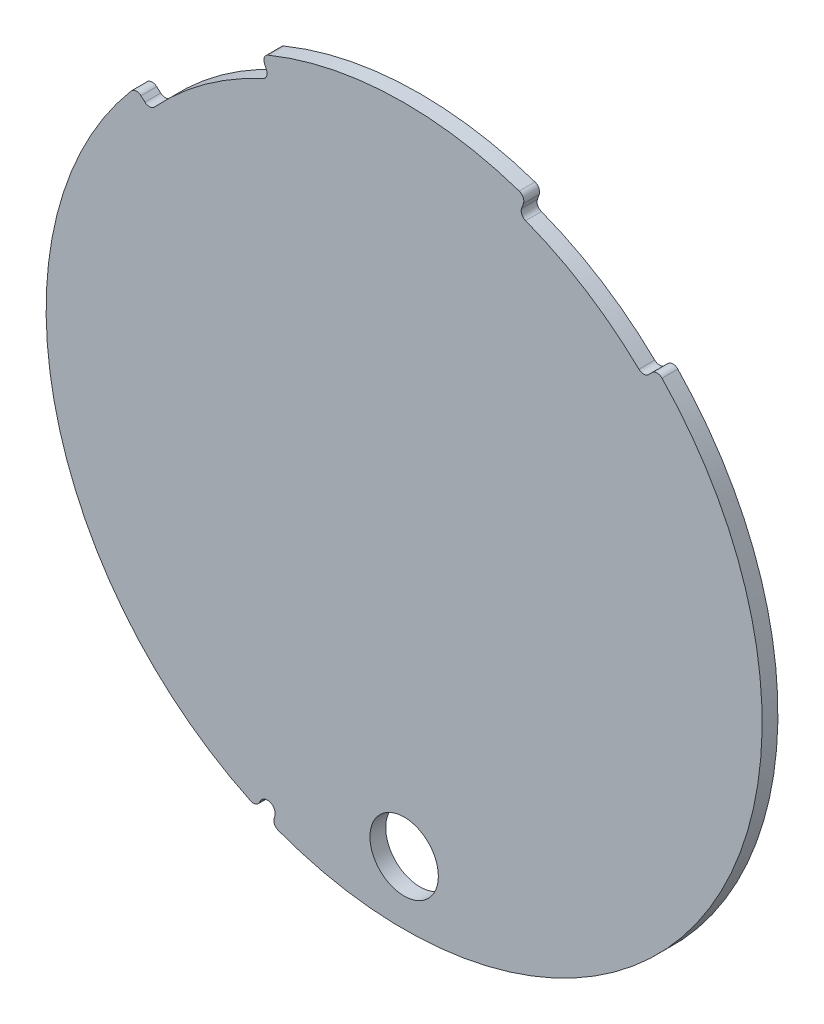
SolidWorks part; units mm, degrees
ref_plane "Alzado" through (0, 0, 0) normal (0, 0, 1) x (1, 0, 0)
ref_plane "Planta" through (0, 0, 0) normal (0, 1, 0) x (1, 0, 0)
ref_plane "Vista lateral" through (0, 0, 0) normal (1, 0, 0) x (0, 0, -1)
sketch "Model" plane through (0, 0, 0) normal (0, 0, 1) x (1, 0, 0)
  line L12 (23.9841, 23.7015) -> (20.8347, 18.3355)
  line L13 (20.8347, 18.3355) -> (9.1701, 24.9845)
  line L14 (9.1701, 24.9845) -> (11.9696, 30.4675)
  line L15 (11.9696, 30.4675) -> (23.9841, 23.7015)
  line L16 (23.5645, -22.1803) -> (11.6405, -29.0235)
  line L17 (11.6405, -29.0235) -> (8.6335, -23.7355)
  line L18 (8.6335, -23.7355) -> (20.4535, -16.8923)
  line L19 (20.4535, -16.8923) -> (23.5645, -22.1803)
  line L20 (-5.4405, -24.0979) -> (-8.4734, -29.4636)
  line L21 (-8.4734, -29.4636) -> (-20.5268, -22.4648)
  line L22 (-20.5268, -22.4648) -> (-17.5718, -17.1768)
  line L23 (-17.5718, -17.1768) -> (-5.4405, -24.0979)
  line L24 (6.9505, -26.589) -> (6.7665, -25.2108)
  line L25 (6.7665, -25.2108) -> (6.2386, -23.9493)
  line L26 (6.2386, -23.9493) -> (5.403, -22.8668)
  line L27 (5.403, -22.8668) -> (4.2959, -22.0254)
  line L28 (4.2959, -22.0254) -> (3.0068, -21.5041)
  line L29 (3.0068, -21.5041) -> (1.6493, -21.3393)
  line L30 (1.6493, -21.3393) -> (0.2952, -21.5305)
  line L31 (0.2952, -21.5305) -> (-0.9834, -22.077)
  line L32 (-0.9834, -22.077) -> (-2.0739, -22.9397)
  line L33 (-2.0739, -22.9397) -> (-2.8882, -24.0384)
  line L34 (-2.8882, -24.0384) -> (-3.3914, -25.31)
  line L35 (-3.3914, -25.31) -> (-3.5485, -26.6915)
  line L36 (-4.4685, -32.0246) -> (-3.5485, -26.6915)
  line L37 (7.8915, -32.0205) -> (11.0678, -31.275)
  line L38 (11.0678, -31.275) -> (14.108, -30.2492)
  line L39 (14.108, -30.2492) -> (16.9999, -28.9593)
  line L40 (16.9999, -28.9593) -> (19.7314, -27.4213)
  line L41 (19.7314, -27.4213) -> (22.2902, -25.6513)
  line L42 (22.2902, -25.6513) -> (24.6641, -23.6655)
  line L43 (24.6641, -23.6655) -> (26.841, -21.4799)
  line L44 (26.841, -21.4799) -> (28.8088, -19.1106)
  line L45 (28.8088, -19.1106) -> (30.5551, -16.5737)
  line L46 (30.5551, -16.5737) -> (32.0679, -13.8853)
  line L47 (32.0679, -13.8853) -> (33.3349, -11.0616)
  line L48 (33.3349, -11.0616) -> (34.344, -8.1185)
  line L49 (34.344, -8.1185) -> (35.083, -5.0721)
  line L50 (35.083, -5.0721) -> (35.5397, -1.9387)
  line L51 (35.5397, -1.9387) -> (35.702, 1.2658)
  line L52 (35.702, 1.2658) -> (35.5575, 4.5252)
  line L53 (35.5575, 4.5252) -> (35.105, 7.7563)
  line L54 (35.105, 7.7563) -> (34.3609, 10.8774)
  line L55 (34.3609, 10.8774) -> (33.3403, 13.875)
  line L56 (33.3403, 13.875) -> (32.058, 16.7354)
  line L57 (32.058, 16.7354) -> (30.5289, 19.445)
  line L58 (30.5289, 19.445) -> (28.7681, 21.9903)
  line L59 (28.7681, 21.9903) -> (26.7902, 24.3576)
  line L60 (26.7902, 24.3576) -> (24.6104, 26.5334)
  line L61 (24.6104, 26.5334) -> (22.2435, 28.504)
  line L62 (22.2435, 28.504) -> (19.7044, 30.2558)
  line L63 (19.7044, 30.2558) -> (17.008, 31.7752)
  line L64 (17.008, 31.7752) -> (14.1693, 33.0487)
  line L65 (14.1693, 33.0487) -> (11.2032, 34.0627)
  line L66 (11.2032, 34.0627) -> (8.1245, 34.8034)
  line L67 (8.1245, 34.8034) -> (4.9482, 35.2574)
  line L68 (4.9482, 35.2574) -> (1.6892, 35.411)
  line L69 (1.6892, 35.411) -> (-1.5698, 35.2552)
  line L70 (-1.5698, 35.2552) -> (-4.7458, 34.7991)
  line L71 (-4.7458, 34.7991) -> (-7.824, 34.0563)
  line L72 (-7.824, 34.0563) -> (-10.7894, 33.0405)
  line L73 (-10.7894, 33.0405) -> (-13.6273, 31.7651)
  line L74 (-13.6273, 31.7651) -> (-16.3227, 30.2438)
  line L75 (-16.3227, 30.2438) -> (-18.8606, 28.4903)
  line L76 (-18.8606, 28.4903) -> (-21.2262, 26.5182)
  line L77 (-21.2262, 26.5182) -> (-23.4046, 24.341)
  line L78 (-23.4046, 24.341) -> (-25.3808, 21.9723)
  line L79 (-25.3808, 21.9723) -> (-27.14, 19.4259)
  line L80 (-27.14, 19.4259) -> (-28.6673, 16.7153)
  line L81 (-28.6673, 16.7153) -> (-29.9477, 13.854)
  line L82 (-29.9477, 13.854) -> (-30.9663, 10.8558)
  line L83 (-30.9663, 10.8558) -> (-31.7083, 7.7341)
  line L84 (-31.7083, 7.7341) -> (-32.1587, 4.5028)
  line L85 (-32.1587, 4.5028) -> (-32.301, 1.2432)
  line L86 (-32.301, 1.2432) -> (-32.1366, -1.9611)
  line L87 (-32.1366, -1.9611) -> (-31.6779, -5.0943)
  line L88 (-31.6779, -5.0943) -> (-30.9369, -8.1401)
  line L89 (-30.9369, -8.1401) -> (-29.9258, -11.0825)
  line L90 (-29.9258, -11.0825) -> (-28.6569, -13.9055)
  line L91 (-28.6569, -13.9055) -> (-27.1423, -16.5929)
  line L92 (-27.1423, -16.5929) -> (-25.3943, -19.1286)
  line L93 (-25.3943, -19.1286) -> (-23.425, -21.4966)
  line L94 (-23.425, -21.4966) -> (-21.2466, -23.6807)
  line L95 (-21.2466, -23.6807) -> (-18.8713, -25.665)
  line L96 (-18.8713, -25.665) -> (-16.3114, -27.4332)
  line L97 (-16.3114, -27.4332) -> (-13.5789, -28.9694)
  line L98 (-13.5789, -28.9694) -> (-10.6861, -30.2574)
  line L99 (-10.6861, -30.2574) -> (-7.6453, -31.2812)
  line L100 (-7.6453, -31.2812) -> (-4.4685, -32.0246)
  line L101 (6.9505, -26.589) -> (7.8915, -32.0205)
  point P1 (-4.4685, -32.0246)
  point P2 (-10.7894, 33.0405)
sketch "Croquis3" plane through (0, 0, 0) normal (0, 0, 1) x (1, 0, 0)
  line L0 (-19.3008, -18.5746) -> (-7.1406, -25.5122) construction
  line L1 (-19.3008, -18.5746) -> (-22.3732, -23.9598) construction
  line L2 (-7.1406, -25.5122) -> (-10.213, -30.8974) construction
  line L3 (-22.3732, -23.9598) -> (-10.213, -30.8974) construction
  line L4 (6.9334, -25.1498) -> (19.0493, -18.1352) construction
  line L5 (6.9334, -25.1498) -> (10.0398, -30.5154) construction
  line L6 (19.0493, -18.1352) -> (22.1558, -23.5009) construction
  line L7 (10.0398, -30.5154) -> (22.1558, -23.5009) construction
  line L8 (10.2361, 28.9943) -> (22.4348, 22.1246) construction
  line L9 (10.2361, 28.9943) -> (7.1938, 23.592) construction
  line L10 (22.4348, 22.1246) -> (19.3925, 16.7223) construction
  line L11 (7.1938, 23.592) -> (19.3925, 16.7223) construction
  line L12 (0, 0) -> (0, -28.0037) construction
  line L13 (0, 0) -> (-6.3752, -33.4001) construction
  line L14 (-5.1573, -27.0193) -> (-6.2808, -32.9053)
  line L15 (5.1573, -27.0193) -> (6.2808, -32.9053)
  line L31 (7.4092, 23.4707) -> (7.7711, 24.617) construction
  circle A0 centre (0, 0) radius 34.0031 construction
  circle A1 centre (0, -28.0037) radius 5.2504 construction
  arc A2 (-5.1573, -27.0193) -> (5.1573, -27.0193) centre (0, -28.0037) cw
  arc A3 (-6.873, -33.3012) -> (6.873, -33.3012) centre (0, 0) cw
  arc A5 (-6.2808, -32.9053) -> (-6.873, -33.3012) centre (-6.7719, -32.8115) cw
  arc A6 (6.2808, -32.9053) -> (6.873, -33.3012) centre (6.7719, -32.8115) ccw
  point P0 (-5.1573, -27.0193)
  dimension "D13" = 68.0062
  dimension "D14" = 10.5008
  dimension "D16" = 0.5
  dimension "D1" = 28.0037
  dimension "D2" = 6.2
  dimension "D3" = 14
  dimension "D4" = 18.5746
  dimension "D5" = 18.1352
  dimension "D6" = 16.7223
  dimension "D7" = 23.592
  dimension "D8" = 25.5122
  dimension "D9" = 25.1498
  dimension "D10" = 7.1938
  dimension "D11" = 6.9334
  dimension "D12" = 7.1406
extrude "Saliente-Extruir2" add sketch "Croquis3" along normal blind 1.5
sketch "Croquis5" plane through (0, 0, 0) normal (0, 0, 1) x (1, 0, 0)
  circle A0 centre (0, -28.0037) radius 5.2504 construction
  circle A1 centre (0, 0) radius 34.0031 construction
  circle A2 centre (0, -28.0037) radius 5.2504 construction
  circle A3 centre (0, 0) radius 34.0031
  circle A4 centre (0, -28.0037) radius 3.25
  dimension "D1" = 6.5
extrude "Saliente-Extruir3" add sketch "Croquis5" along normal blind 1.5 contours A3 | A4
sketch "Croquis4" plane through (0, 0, 0) normal (0, 0, 1) x (1, 0, 0)
  line L0 (10.2361, 28.9943) -> (22.4348, 22.1246) construction
  line L1 (22.4348, 22.1246) -> (19.3925, 16.7223) construction
  line L2 (7.1938, 23.592) -> (19.3925, 16.7223) construction
  line L3 (10.2361, 28.9943) -> (7.1938, 23.592) construction
  line L4 (10.2361, 28.9943) -> (22.4348, 22.1246) construction
  line L5 (22.4348, 22.1246) -> (19.3925, 16.7223) construction
  line L6 (7.1938, 23.592) -> (19.3925, 16.7223) construction
  line L7 (10.2361, 28.9943) -> (7.1938, 23.592) construction
  line L24 (0, 0) -> (17.263, 27.1851) construction
  line L26 (22.7594, 22.7826) -> (24.0316, 24.056)
  line L27 (10.941, 30.2875) -> (11.5525, 31.9804)
  arc A0 (6.873, -33.3012) -> (-6.873, -33.3012) centre (0, 0) ccw construction
  arc A1 (24.0316, 24.056) -> (11.5525, 31.9804) centre (0, 0) ccw
  arc A2 (10.941, 30.2875) -> (22.7594, 22.7826) centre (0, 0) cw
  point P14 (16.0978, -27.0081)
  point P19 (17.263, 27.1851)
  dimension "D4" = 34.0031
  dimension "D1" = 14
  dimension "D3" = 1.8
  dimension "D2" = 32.2031
extrude "Cortar-Extruir6" cut sketch "Croquis4" along normal blind 1.5
fillet "Redondeo2" radius 0.65 4 edges at (11.5525, 31.9804, 0.75) (24.0316, 24.056, 0.75) (22.7594, 22.7826, 0.75) (10.941, 30.2875, 0.75)
ref_axis "Eje1" through (0, 0, -0.075) along (0, 0, 1)
pattern_circular "MatrizC2" [suppressed] count 2 every 182 about axis through (0, 0, -0.075) along (0, 0, 1) of bodies 111
pattern_circular "MatrizC3" [suppressed] count 2 every 243 about axis through (0, 0, -0.075) along (0, 0, 1) of bodies 113
sketch "Croquis6" plane through (0, 0, 1.5) normal (0, 0, 1) x (1, 0, 0)
  line L0 (0, 0) -> (-19.9865, 27.5091) construction
  line L1 (-24.1372, 21.3128) -> (-25.4888, 22.5063)
  line L2 (-12.8109, 29.5418) -> (-13.5283, 31.1961)
  line L3 (0, 0) -> (0, 35.0983) construction
  line L5 (11.1596, 30.8928) -> (11.3295, 31.3631)
  line L6 (23.5677, 23.5917) -> (23.2143, 23.2379)
  arc A0 (10.9271, 32.1995) -> (24.4958, 23.5831) centre (0, 0) ccw construction
  arc A1 (-24.1372, 21.3128) -> (-12.8109, 29.5418) centre (0, 0) cw
  arc A9 (11.3295, 31.3631) -> (10.9271, 32.1995) centre (10.7182, 31.584) ccw
  arc A10 (10.9271, 32.1995) -> (24.4958, 23.5831) centre (0, 0) ccw
  arc A11 (24.4958, 23.5831) -> (23.5677, 23.5917) centre (24.0276, 23.1323) ccw
  arc A12 (22.3042, 23.2284) -> (23.2143, 23.2379) centre (22.7544, 23.6973) ccw
  arc A13 (22.3042, 23.2284) -> (11.5381, 30.0651) centre (0, 0) ccw
  arc A14 (11.1596, 30.8928) -> (11.5381, 30.0651) centre (11.771, 30.672) ccw
  arc A16 (-13.5283, 31.1961) -> (-25.4888, 22.5063) centre (0, 0) ccw
  point P10 (-18.3134, 26.1542)
  point P16 (-18.9267, 26.0503)
  dimension "D1" = 0
  dimension "D4" = 32.2
  dimension "D2" = 14
  dimension "D3" = 36
extrude "Cortar-Extruir7" cut sketch "Croquis6" against normal blind 1.5
fillet "Redondeo3" radius 0.65 4 edges at (-24.1372, 21.3128, 0.75) (-13.5283, 31.1961, 0.75) (-12.8109, 29.5418, 0.75) (-25.4888, 22.5063, 0.75)
sketch "Croquis7" plane through (0, 0, 1.5) normal (0, 0, 1) x (1, 0, 0)
  line L0 (0, 0) -> (-13.2861, -31.3) construction
  line L1 (-13.9886, -30.9924) -> (-13.6766, -30.3011)
  line L2 (-13.6766, -30.3011) -> (0, 0) construction
  line L3 (-12.5767, -31.5917) -> (-12.2962, -30.887)
  line L4 (0, 0) -> (0, -34.0031) construction
  arc A0 (-25.9225, 22.0053) -> (24.4958, 23.5831) centre (0, 0) ccw construction
  arc A1 (-12.2962, -30.887) -> (-13.6766, -30.3011) centre (-12.993, -30.6096) ccw
  arc A2 (-12.5767, -31.5917) -> (-13.9886, -30.9924) centre (0, 0) cw
  arc M12 (-25.9225, 22.0053) -> (24.4958, 23.5831) centre (0, 0) ccw
  dimension "D1" = 1.5
  dimension "D2" = 0.75
  dimension "D3" = 23
extrude "Cortar-Extruir8" cut sketch "Croquis7" against normal blind 1.5 contours L3 A1 L1 M12 region at (-13.0209, -30.6752, 1.5)
fillet "Redondeo4" radius 0.65 2 edges at (-12.5767, -31.5917, 0.75) (-13.9886, -30.9924, 0.75)
equation "\"D2@Croquis4\"=\"D4@Croquis4\"-1.8"
equation "\"D2@Croquis7\"=\"D1@Croquis7\"/2"
